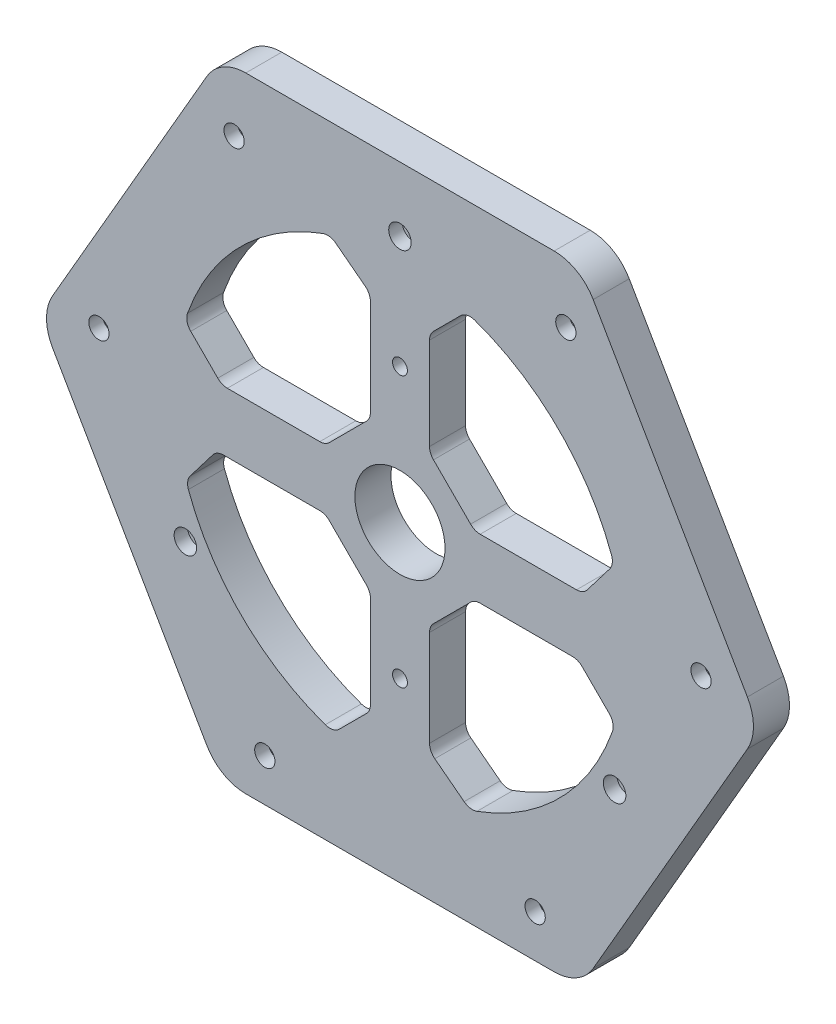
SolidWorks part; units mm, degrees
ref_plane "Front Plane" through (0, 0, 0) normal (0, 0, 1) x (1, 0, 0)
ref_plane "Top Plane" through (0, 0, 0) normal (0, 1, 0) x (1, 0, 0)
ref_plane "Right Plane" through (0, 0, 0) normal (1, 0, 0) x (0, 0, -1)
sketch "Sketch1" plane through (0, 0, 0) normal (0, 0, 1) x (1, 0, 0)
  line L1 (40, 69.282) -> (-40, 69.282)
  line L2 (-40, 69.282) -> (-80, 0)
  line L3 (-80, 0) -> (-40, -69.282)
  line L4 (-40, -69.282) -> (40, -69.282)
  line L5 (40, -69.282) -> (80, 0)
  line L6 (80, 0) -> (40, 69.282)
  circle A0 centre (0, 0) radius 69.282 construction
  dimension "D1" = 80
extrude "Boss-Extrude1" add sketch "Sketch1" along normal blind 8
sketch "Sketch2" plane through (0, 0, 8) normal (0, 0, 1) x (1, 0, 0)
  line L0 (-60, 34.641) -> (0, 0) construction
  line L1 (-40, 69.282) -> (-80, 0) construction
  line L2 (0, 0) -> (0, -69.282) construction
  line L3 (-40, -69.282) -> (40, -69.282) construction
  line L4 (0, 0) -> (60, 34.641) construction
  line L5 (80, 0) -> (40, 69.282) construction
  circle A0 centre (-36.8161, 55.8968) radius 2.25
  circle A1 centre (-66.8161, 3.9353) radius 2.25
  circle A2 centre (36.8161, 55.8968) radius 2.25
  circle A3 centre (66.8161, 3.9353) radius 2.25
  circle A4 centre (30, -59.8321) radius 2.25
  circle A5 centre (-30, -59.8321) radius 2.25
  point P26 (0, 0)
  dimension "D1" = 4.5
  dimension "D2" = 30
  dimension "D3" = 3
extrude "Cut-Extrude1" cut sketch "Sketch2" against normal blind 28
fillet "Fillet1" radius 10 6 edges at (40, -69.282, 4) (80, 0, 4) (40, 69.282, 4) (-40, 69.282, 4) (-40, -69.282, 4) (-80, 0, 4)
sketch "Sketch5" plane through (0, 0, 8) normal (0, 0, 1) x (1, 0, 0)
  circle A0 centre (0, 0) radius 55 construction
  circle A1 centre (0, 55) radius 1.65
  circle A2 centre (47.6314, -27.5) radius 1.65
  circle A3 centre (-47.6314, -27.5) radius 1.65
  point P12 (0, 0)
  dimension "D1" = 3.3
  dimension "D2" = 110
  dimension "D3" = 3
extrude "Cut-Extrude3" cut sketch "Sketch5" against normal blind 45
sketch "Sketch10" plane through (0, 0, 0) normal (0, 0, -1) x (-1, 0, 0)
  circle A0 centre (-30, -59.8321) radius 4
  circle A1 centre (-66.8161, 3.9353) radius 4
  circle A2 centre (-36.8161, 55.8968) radius 4
  circle A3 centre (36.8161, 55.8968) radius 4
  circle A4 centre (66.8161, 3.9353) radius 4
  circle A5 centre (30, -59.8321) radius 4
  point P16 (0, 0)
  dimension "D1" = 8
  dimension "D2" = 8
  dimension "D3" = 3
extrude "Cut-Extrude4" cut sketch "Sketch10" against normal blind 5
sketch "Sketch11" plane through (0, 0, 0) normal (0, 0, -1) x (-1, 0, 0)
  line L0 (0, 53.35) -> (0, 0) construction
  line L3 (-6.5562, -49.5683) -> (-6.5562, -6.6288)
  line L5 (6.5562, -49.5683) -> (6.5562, -6.6288)
  line L8 (-49.5586, -6.6288) -> (-6.5562, -6.6288)
  line L10 (-49.5586, 6.6288) -> (-6.5562, 6.6288)
  line L14 (6.5562, 6.6288) -> (49.5586, 6.6288)
  line L16 (6.5562, -6.6288) -> (49.5586, -6.6288)
  line L18 (-6.5562, 6.6288) -> (-6.5562, 49.5683)
  line L19 (6.5562, 6.6288) -> (6.5562, 49.5683)
  circle A0 centre (0, 55) radius 1.65 construction
  arc A1 (-6.5562, 49.5683) -> (-49.5586, 6.6288) centre (0, 0) ccw
  arc A2 (-49.5586, -6.6288) -> (-6.5562, -49.5683) centre (0, 0) ccw
  arc A3 (49.5586, 6.6288) -> (6.5562, 49.5683) centre (0, 0) ccw
  arc A4 (6.5562, -49.5683) -> (49.5586, -6.6288) centre (0, 0) ccw
  dimension "D1" = 100
extrude "Cut-Extrude5" cut sketch "Sketch11" against normal blind 10
chamfer "Chamfer1" distance 10 angle 45 12 edges at (-6.5562, -6.6288, 4) (-49.5586, -6.6288, 4) (-6.5562, -49.5683, 4) (6.5562, -49.5683, 4) (6.5562, -6.6288, 4) (49.5586, -6.6288, 4) (6.5562, 49.5683, 4) (49.5586, 6.6288, 4) (6.5562, 6.6288, 4) (-49.5586, 6.6288, 4) (-6.5562, 6.6288, 4) (-6.5562, 49.5683, 4) first distance on face at (-28.0574, -6.6288, 4) first distance on face at (-31.6934, -31.7399, 4) first distance on face at (-6.5562, -28.0986, 4) first distance on face at (31.6934, -31.7399, 4) first distance on face at (6.5562, -28.0986, 4) first distance on face at (28.0574, -6.6288, 4) first distance on face at (6.5562, 28.0986, 4) first distance on face at (31.6934, 31.7399, 4) first distance on face at (28.0574, 6.6288, 4) first distance on face at (-28.0574, 6.6288, 4) first distance on face at (-6.5562, 28.0986, 4) first distance on face at (-31.6934, 31.7399, 4)
sketch "Sketch12" plane through (0, 0, 0) normal (0, 0, -1) x (-1, 0, 0)
  circle A0 centre (0, 0) radius 10
  dimension "D1" = 20
extrude "Cut-Extrude6" cut sketch "Sketch12" against normal blind 25.5
sketch "Sketch13" plane through (0, 0, 0) normal (0, 0, -1) x (-1, 0, 0)
  line L0 (0, 0) -> (0, 30) construction
  line L1 (0, 0) -> (29.9436, 0) construction
  circle A0 centre (0, 30) radius 1.65
  circle A1 centre (0, -30) radius 1.65
  dimension "D2" = 3.3
  dimension "D1" = 30
extrude "Cut-Extrude7" cut sketch "Sketch13" against normal blind 10
sketch "Sketch14" plane through (0, 0, 0) normal (0, 0, -1) x (-1, 0, 0)
  circle A0 centre (0, -30) radius 2.55
  circle A1 centre (0, 30) radius 2.55
  dimension "D1" = 5.1
  dimension "D2" = 5.1
extrude "Cut-Extrude8" cut sketch "Sketch14" against normal blind 2.3
fillet "Fillet2" radius 3 24 edges at (-14.7598, -47.7718, 4) (-6.5562, -39.5683, 4) (-6.5562, -16.6288, 4) (-16.5562, -6.6288, 4) (-47.5072, -15.5907, 4) (-40.6599, -6.6288, 4) (15.5211, -47.5299, 4) (6.5562, -40.6595, 4) (6.5562, -16.6288, 4) (16.5562, -6.6288, 4) (39.5586, -6.6288, 4) (47.7524, -14.8226, 4) (6.5562, 39.5683, 4) (14.7598, 47.7718, 4) (47.5072, 15.5907, 4) (40.6599, 6.6288, 4) (16.5562, 6.6288, 4) (6.5562, 16.6288, 4) (-47.7524, 14.8226, 4) (-39.5586, 6.6288, 4) (-16.5562, 6.6288, 4) (-6.5562, 16.6288, 4) (-6.5562, 40.6595, 4) (-15.5211, 47.5299, 4)
sketch "Sketch15" plane through (0, 0, 8) normal (0, 0, 1) x (1, 0, 0)
  circle A0 centre (-47.6314, -27.5) radius 2.5
  circle A1 centre (0, 55) radius 2.5
  circle A2 centre (47.6314, -27.5) radius 2.5
  point P10 (0, 0)
  dimension "D1" = 5
  dimension "D2" = 3
extrude "Cut-Extrude9" cut sketch "Sketch15" against normal blind 3
sketch "Sketch18" plane through (0, 0, 0) normal (0, 0, -1) x (-1, 0, 0)
  line L0 (-66.8161, 3.9353) -> (-61.8161, 12.5956) construction
  line L1 (-77.1132, 5) -> (-42.8868, 64.282) construction
  line L2 (0, 0) -> (0, -69.282) construction
  line L3 (-61.8161, 12.5956) -> (-73.698, 19.4556) construction
  line L4 (34.2265, -69.282) -> (-34.2265, -69.282) construction
  line L5 (-41.8161, 47.2366) -> (-53.698, 54.0966) construction
  line L6 (-36.8161, 55.8968) -> (-41.8161, 47.2366) construction
  line L7 (36.8161, 55.8968) -> (41.8161, 47.2366) construction
  line L8 (41.8161, 47.2366) -> (53.698, 54.0966) construction
  line L9 (61.8161, 12.5956) -> (73.698, 19.4556) construction
  line L10 (66.8161, 3.9353) -> (61.8161, 12.5956) construction
  line L11 (30, -59.8321) -> (20, -59.8321) construction
  line L12 (20, -59.8321) -> (20, -73.5521) construction
  line L13 (-20, -59.8321) -> (-20, -73.5521) construction
  line L14 (-30, -59.8321) -> (-20, -59.8321) construction
  line L15 (0, 0) -> (-78.453, 0) construction
  arc A0 (-77.1132, 5) -> (-77.1132, -5) centre (-68.453, 0) ccw construction
  point P28 (0, 0)
  dimension "D1" = 10
  dimension "D2" = 13.72
  dimension "D3" = 3
